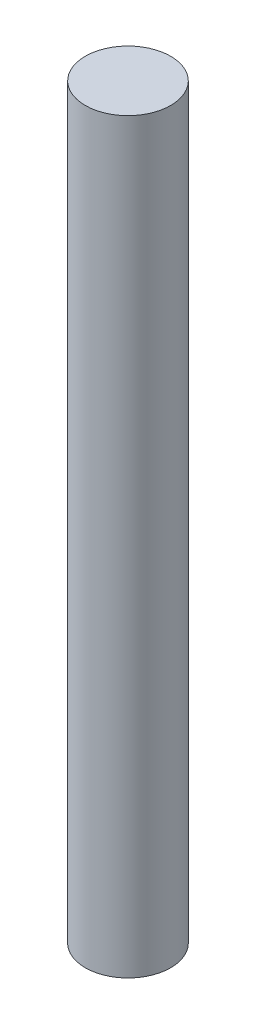
SolidWorks part; units mm, degrees
material "Brass"
ref_plane "Front Plane" through (0, 0, 0) normal (0, 0, 1) x (1, 0, 0)
ref_plane "Top Plane" through (0, 0, 0) normal (0, 1, 0) x (1, 0, 0)
ref_plane "Right Plane" through (0, 0, 0) normal (1, 0, 0) x (0, 0, -1)
sketch "Sketch1" plane through (0, 0, 0) normal (0, 1, 0) x (1, 0, 0)
  circle A0 centre (0, 0) radius 1
  dimension "D1" = 2
extrude "Boss-Extrude1" add sketch "Sketch1" along normal blind 17.5
scale "Scale1" scale about centroid uniform scaling yes scale factor 6
